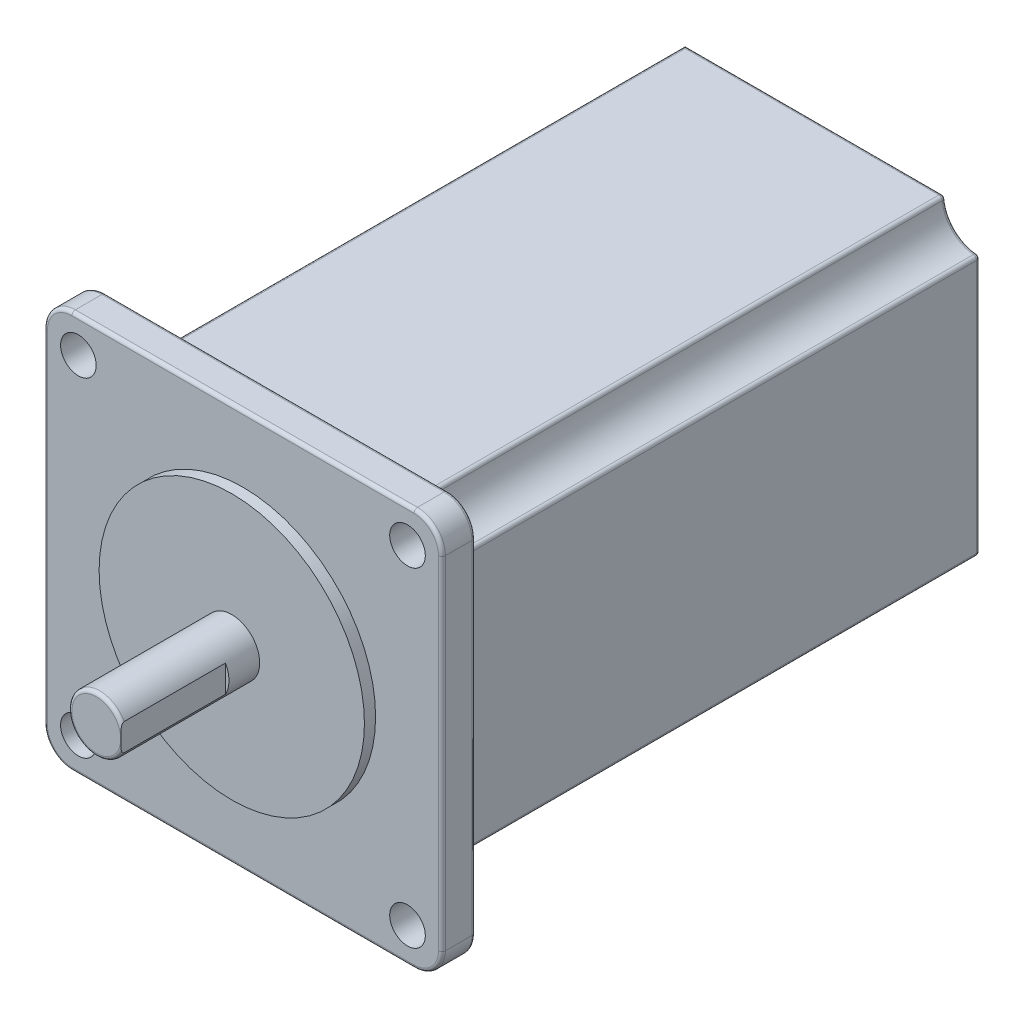
SolidWorks part; units mm, degrees
ref_plane "Ön Düzlem" through (0, 0, 0) normal (0, 0, 1) x (1, 0, 0)
ref_plane "Üst Düzlem" through (0, 0, 0) normal (0, 1, 0) x (1, 0, 0)
ref_plane "Sağ Düzlem" through (0, 0, 0) normal (1, 0, 0) x (0, 0, -1)
sketch "Çizim1" plane through (0, 0, 0) normal (0, 0, 1) x (1, 0, 0)
  line L1 (-38.3135, 28.5173) -> (-38.3135, -20.4827)
  line L3 (-34.3135, 32.5173) -> (14.6865, 32.5173)
  line L5 (18.6865, 28.5173) -> (18.6865, -20.4827)
  line L6 (14.6865, -24.4827) -> (-34.3135, -24.4827)
  arc A0 (-38.3135, -20.4827) -> (-34.3135, -24.4827) centre (-34.3135, -20.4827) ccw
  arc A1 (18.6865, -20.4827) -> (14.6865, -24.4827) centre (14.6865, -20.4827) cw
  arc A2 (14.6865, 32.5173) -> (18.6865, 28.5173) centre (14.6865, 28.5173) cw
  arc A3 (-34.3135, 32.5173) -> (-38.3135, 28.5173) centre (-34.3135, 28.5173) ccw
  circle A4 centre (-33.3835, 27.5873) radius 2.55
  circle A5 centre (-33.3835, -19.5527) radius 2.55
  circle A6 centre (13.7565, -19.5527) radius 2.55
  circle A7 centre (13.7565, 27.5873) radius 2.55
  circle A8 centre (-9.8135, 4.0173) radius 4
  circle A9 centre (-9.8135, 4.0173) radius 19.05
  dimension "D3" = 4
  dimension "D4" = 5.1
  dimension "D5" = 4.93
  dimension "D6" = 4.93
  dimension "D7" = 5.1
  dimension "D8" = 4.93
  dimension "D9" = 4.93
  dimension "D10" = 5.1
  dimension "D11" = 4.93
  dimension "D12" = 4.93
  dimension "D13" = 5.1
  dimension "D14" = 4.93
  dimension "D15" = 4.93
  dimension "D16" = 8
  dimension "D17" = 38.1
  dimension "D18" = 28.5
  dimension "D19" = 28.5
extrude "Yükseklik-Ekstrüzyon1" add sketch "Çizim1" against normal blind 4.8 contours L3 A3 L1 A0 L6 A1 L5 A2 A9 A7 A6 A5 A4 | A9 A8 | A8 region at (-36.5719, 30.7757, 0) region at (-9.8135, 4.0173, 0) region at (-28.3247, 4.0173, 0)
sketch "Çizim2" plane through (0, 0, 0) normal (0, 0, 1) x (1, 0, 0)
  line L0 (-38.3135, 28.5173) -> (-38.3135, -20.4827) construction
  line L2 (-38.3135, 32.5173) -> (-38.3135, -24.4827)
  line L3 (-38.3135, -24.4827) -> (18.6865, -24.4827)
  line L4 (18.6865, -24.4827) -> (18.6865, 32.5173)
  line L5 (18.6865, 32.5173) -> (-38.3135, 32.5173)
  line L6 (-34.3135, 32.5173) -> (14.6865, 32.5173) construction
  line L7 (-9.8135, -24.4827) -> (-9.8135, 32.5173)
  circle A0 centre (-9.8135, 4.0173) radius 19
  dimension "D5" = 38
  dimension "D1" = 0
  dimension "D2" = 57
  dimension "D3" = 0
  dimension "D4" = 57
extrude "Yükseklik-Ekstrüzyon2" add sketch "Çizim2" along normal blind 1.6 contours L7 A0 | L7 A0 region at (-1.7497, 4.0173, 0) region at (-17.8774, 4.0173, 0)
sketch "Çizim3" plane through (0, 0, 1.6) normal (0, 0, 1) x (1, 0, 0)
  circle A0 centre (-9.8135, 4.0173) radius 4
  circle A1 centre (-9.8135, 4.0173) radius 19 construction
  dimension "D1" = 8
extrude "Yükseklik-Ekstrüzyon3" add sketch "Çizim3" along normal blind 19.4
sketch "Çizim4" plane through (0, 0, 21) normal (0, 0, 1) x (1, 0, 0)
  line L0 (-13.8135, 4.0173) -> (-5.8135, 4.0173)
  line L1 (-9.8135, 8.0173) -> (-9.8135, 0.0173)
  line L2 (-13.8135, 4.0173) -> (-6.3135, 4.0173)
  line L3 (-6.3135, 4.0173) -> (-6.3135, 6.246)
  line L4 (-6.3135, 6.246) -> (-5.0245, 6.246)
  line L5 (-6.3135, 4.0173) -> (-6.3135, 1.5772)
  line L6 (-6.3135, 1.5772) -> (-5.0245, 1.5772)
  line L7 (-5.0245, 1.5772) -> (-5.0245, 6.246)
  circle A0 centre (-9.8135, 4.0173) radius 4 construction
  circle A1 centre (-9.8135, 4.0173) radius 4 construction
  circle M6 centre (-9.8135, 4.0173) radius 4
extrude "Kes-Ekstrüzyon1" cut sketch "Çizim4" against normal blind 15 contours L3 L0 M6 | L0 L5 M6 | L6 L7 L4 L3 L5 M6 region at (-6.1124, 4.7499, 21) region at (-6.1124, 3.2847, 21) region at (-5.5459, 3.8822, 21)
sketch "Çizim5" plane through (0, 0, -4.8) normal (0, 0, -1) x (-1, 0, 0)
  line L0 (-13.7565, 22.6573) -> (-13.7565, -14.6227)
  line L1 (-8.8265, -19.5527) -> (28.4535, -19.5527)
  line L2 (33.3835, -14.6227) -> (33.3835, 22.6573)
  line L3 (28.4535, 27.5873) -> (-8.8265, 27.5873)
  circle A0 centre (-13.7565, 27.5873) radius 4.93
  circle A1 centre (33.3835, 27.5873) radius 4.93
  circle A2 centre (-13.7565, -19.5527) radius 4.93
  circle A3 centre (33.3835, -19.5527) radius 4.93
extrude "Yükseklik-Ekstrüzyon4" add sketch "Çizim5" along normal blind 77.2 contours A3 L2 A1 L3 A0 L0 A2 L1 region at (-9.8135, 4.0173, -4.8)
fillet "Radyus1" radius 0.5 31 edges at (-37.1419, 31.3457, -4.8) (-38.3135, 4.0173, -4.8) (-37.1419, -23.3111, -4.8) (-9.8135, -24.4827, -4.8) (17.5149, -23.3111, -4.8) (18.6865, 4.0173, -4.8) (17.5149, 31.3457, -4.8) (-37.1419, 31.3457, 0) (-38.3135, 4.0173, 0) (-37.1419, -23.3111, 0) (-9.8135, -24.4827, 0) (17.5149, -23.3111, 0) (18.6865, 4.0173, 0) (17.5149, 31.3457, 0) (-28.4535, 27.5873, -43.4) (-33.3835, 22.6573, -43.4) (-33.3835, -14.6227, -43.4) (-29.8975, -16.0667, -82) (-28.4535, -19.5527, -43.4) (-9.8135, -19.5527, -82) (10.2705, -16.0667, -82) (8.8265, -19.5527, -43.4) (13.7565, -14.6227, -43.4) (-9.8135, 27.5873, -82) (8.8265, 27.5873, -43.4) (10.2705, 24.1013, -82) (13.7565, 22.6573, -43.4) (13.7565, 4.0173, -82) (-13.8135, 4.0173, 21) (-9.8135, 32.5173, -4.8) (-9.8135, 32.5173, 0)
